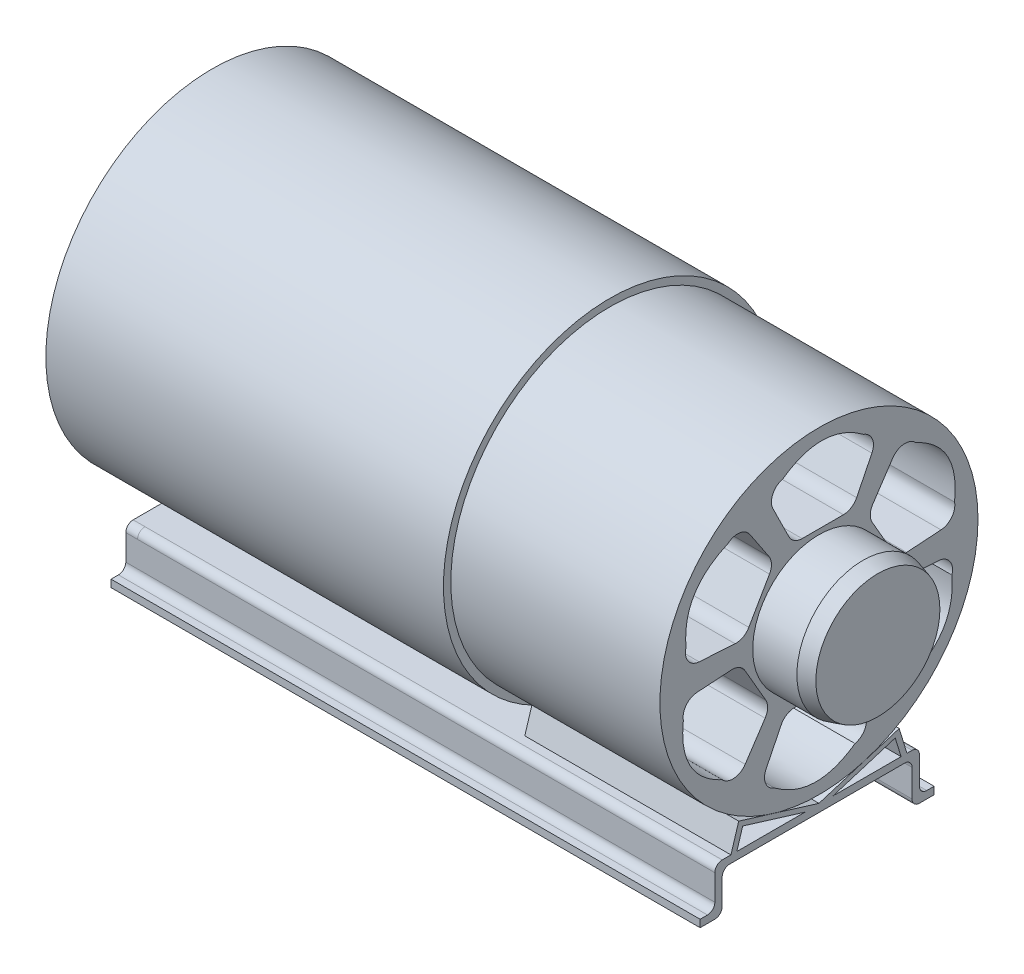
SolidWorks part; units mm, degrees
material "1060 Alloy"
ref_plane "Front Plane" through (0, 0, 0) normal (0, 0, 1) x (1, 0, 0)
ref_plane "Top Plane" through (0, 0, 0) normal (0, 1, 0) x (1, 0, 0)
ref_plane "Right Plane" through (0, 0, 0) normal (1, 0, 0) x (0, 0, -1)
sketch "Sketch1" plane through (0, 0, 0) normal (1, 0, 0) x (0, 0, -1)
  circle A0 centre (0, 0) radius 113
  dimension "D1" = 226
extrude "Boss-Extrude1" add sketch "Sketch1" against normal blind 412
sketch "Sketch2" plane through (0, 0, 0) normal (1, 0, 0) x (0, 0, -1)
  circle A0 centre (0, 0) radius 108
  circle A1 centre (0, 0) radius 113
  dimension "D1" = 216
extrude "Cut-Extrude1" cut sketch "Sketch2" against normal blind 142
sketch "Sketch3" plane through (0, 0, 0) normal (1, 0, 0) x (0, 0, -1)
  circle A0 centre (0, 0) radius 45
  dimension "D1" = 90
extrude "Boss-Extrude2" add sketch "Sketch3" along normal blind 40
chamfer "Chamfer1" distance 10 angle 16 1 edges at (40, 0, -45) first distance on face at (40, 0, -45)
sketch "Sketch4" plane through (0, 0, 0) normal (1, 0, 0) x (0, 0, -1)
  line L0 (-31.2402, 75.8787) -> (-20.392, 53.9645)
  line L1 (-11.43, 48.401) -> (16.6248, 48.401)
  line L2 (25.5919, 53.9748) -> (35.9576, 74.9748)
  line L3 (50.0927, 64.9942) -> (36.5386, 44.6422)
  line L4 (36.2015, 34.0991) -> (50.2288, 9.803)
  line L5 (59.5394, 4.8242) -> (82.9089, 6.3472)
  line L6 (81.333, -10.8845) -> (56.9306, -9.3223)
  line L7 (47.6314, -14.3018) -> (33.6041, -38.5979)
  line L8 (33.9476, -49.1506) -> (46.9513, -68.6276)
  line L9 (31.2402, -75.8787) -> (20.392, -53.9645)
  line L10 (11.43, -48.401) -> (-16.6248, -48.401)
  line L11 (-25.5919, -53.9748) -> (-35.9576, -74.9748)
  line L12 (-50.0927, -64.9942) -> (-36.5386, -44.6422)
  line L13 (-36.2015, -34.0991) -> (-50.2288, -9.803)
  line L14 (-59.5394, -4.8242) -> (-82.9089, -6.3472)
  line L15 (-81.333, 10.8845) -> (-56.9306, 9.3223)
  line L16 (-47.6314, 14.3018) -> (-33.6041, 38.5979)
  line L17 (-33.9476, 49.1506) -> (-46.9513, 68.6276)
  arc A0 (35.9576, 74.9748) -> (30.3376, 88.8243) centre (26.9905, 79.401) ccw
  arc A1 (-31.2402, 75.8787) -> (-24.4733, 90.0713) centre (-22.2782, 80.3152) cw
  arc A2 (-20.392, 53.9645) -> (-11.43, 48.401) centre (-11.43, 58.401) ccw
  arc A3 (16.6248, 48.401) -> (25.5919, 53.9748) centre (16.6248, 58.401) ccw
  arc A4 (50.0927, 64.9942) -> (65.7673, 66.2301) centre (58.4159, 59.4511) cw
  arc A5 (36.5386, 44.6422) -> (36.2015, 34.0991) centre (44.8617, 39.0991) ccw
  arc A6 (50.2288, 9.803) -> (59.5394, 4.8242) centre (58.8891, 14.803) ccw
  arc A7 (82.9089, 6.3472) -> (92.0928, 18.139) centre (82.2586, 16.3261) ccw
  arc A8 (81.333, -10.8845) -> (90.2407, -23.8411) centre (80.6941, -20.8641) cw
  arc A9 (56.9306, -9.3223) -> (47.6314, -14.3018) centre (56.2917, -19.3018) ccw
  arc A10 (33.6041, -38.5979) -> (33.9476, -49.1506) centre (42.2643, -43.5979) ccw
  arc A11 (46.9513, -68.6276) -> (61.7553, -70.6852) centre (55.2681, -63.075) ccw
  arc A12 (31.2402, -75.8787) -> (24.4733, -90.0713) centre (22.2782, -80.3152) cw
  arc A13 (20.392, -53.9645) -> (11.43, -48.401) centre (11.43, -58.401) ccw
  arc A14 (-16.6248, -48.401) -> (-25.5919, -53.9748) centre (-16.6248, -58.401) ccw
  arc A15 (-35.9576, -74.9748) -> (-30.3376, -88.8243) centre (-26.9905, -79.401) ccw
  arc A16 (-50.0927, -64.9942) -> (-65.7673, -66.2301) centre (-58.4159, -59.4511) cw
  arc A17 (-36.5386, -44.6422) -> (-36.2015, -34.0991) centre (-44.8617, -39.0991) ccw
  arc A18 (-50.2288, -9.803) -> (-59.5394, -4.8242) centre (-58.8891, -14.803) ccw
  arc A19 (-82.9089, -6.3472) -> (-92.0928, -18.139) centre (-82.2586, -16.3261) ccw
  arc A20 (-81.333, 10.8845) -> (-90.2407, 23.8411) centre (-80.6941, 20.8641) cw
  arc A21 (-56.9306, 9.3223) -> (-47.6314, 14.3018) centre (-56.2917, 19.3018) ccw
  arc A22 (-33.6041, 38.5979) -> (-33.9476, 49.1506) centre (-42.2643, 43.5979) ccw
  arc A23 (-46.9513, 68.6276) -> (-61.7553, 70.6852) centre (-55.2681, 63.075) ccw
  spline S0 degree 3 poles (30.3376, 88.8243) (20.5234, 96.0661) (2.1757, 102.6494) (-16.0064, 96.0445) (-24.4733, 90.0713) knots 0.076117 0.076117 0.076117 0.076117 0.512929 0.896674 0.896674 0.896674 0.896674
  spline S1 degree 3 poles (92.0928, 18.139) (93.4574, 30.2592) (89.9848, 49.4405) (75.1738, 61.8842) (65.7673, 66.2301) knots 0.076117 0.076117 0.076117 0.076117 0.512929 0.896674 0.896674 0.896674 0.896674
  spline S2 degree 3 poles (61.7553, -70.6852) (72.9339, -65.8069) (87.8091, -53.2089) (91.1802, -34.1603) (90.2407, -23.8411) knots 0.076117 0.076117 0.076117 0.076117 0.512929 0.896674 0.896674 0.896674 0.896674
  spline S3 degree 3 poles (-30.3376, -88.8243) (-20.5234, -96.0661) (-2.1757, -102.6494) (16.0064, -96.0445) (24.4733, -90.0713) knots 0.076117 0.076117 0.076117 0.076117 0.512929 0.896674 0.896674 0.896674 0.896674
  spline S4 degree 3 poles (-92.0928, -18.139) (-93.4574, -30.2592) (-89.9848, -49.4405) (-75.1738, -61.8842) (-65.7673, -66.2301) knots 0.076117 0.076117 0.076117 0.076117 0.512929 0.896674 0.896674 0.896674 0.896674
  spline S5 degree 3 poles (-61.7553, 70.6852) (-72.9339, 65.8069) (-87.8091, 53.2089) (-91.1802, 34.1603) (-90.2407, 23.8411) knots 0.076117 0.076117 0.076117 0.076117 0.512929 0.896674 0.896674 0.896674 0.896674
  point P80 (0, 0)
  dimension "D1" = 10
  dimension "D2" = 6
extrude "Cut-Extrude2" cut sketch "Sketch4" against normal blind 140
sketch "Sketch5" plane through (0, 0, 0) normal (1, 0, 0) x (0, 0, -1)
  line L0 (0, -113) -> (54.4779, -96.2321)
  line L1 (54.4779, -96.2321) -> (59.773, -113.4357)
  line L2 (59.773, -113.4357) -> (55.773, -113.4357)
  line L3 (55.773, -113.4357) -> (51.7735, -100.4415)
  line L4 (51.7735, -100.4415) -> (0, -116.377)
  line L5 (0, -61.5014) -> (0, -90.8439)
  line L6 (-51.7735, -100.4415) -> (0, -116.377)
  line L7 (-55.773, -113.4357) -> (-51.7735, -100.4415)
  line L8 (-59.773, -113.4357) -> (-55.773, -113.4357)
  line L9 (-54.4779, -96.2321) -> (-59.773, -113.4357)
  line L10 (0, -113) -> (-54.4779, -96.2321)
  circle A0 centre (0, 0) radius 113 construction
  dimension "D1" = 4
  dimension "D2" = 18
  dimension "D3" = 57
  dimension "D4" = 54.1704
extrude "Boss-Extrude3" add sketch "Sketch5" against normal blind 140 separate body contours L0 L10 L9 L8 L7 L6 L4 L3 L2 L1 region at (0, -105.7747, -27.5956)
sketch "Sketch7" plane through (0, -113.4357, 0) normal (0, -1, 0) x (1, 0, 0)
  line L0 (0, -108) -> (0, 108) construction
  line L1 (0, 70.7066) -> (-142, 70.7066)
  line L2 (0, 70.7066) -> (0, -68.2082)
  line L3 (0, -68.2082) -> (-142, -68.2082)
  line L4 (-142, 70.7066) -> (-142, -68.2082)
  line L5 (-142, -113) -> (-142, 113) construction
extrude "Boss-Extrude4" add sketch "Sketch7" along normal blind 5
sketch "Sketch8" plane through (0, -118.4357, 0) normal (0, -1, 0) x (1, 0, 0)
  line L0 (0, 70.7066) -> (-142, 70.7066) construction
  line L1 (-142, 70.7066) -> (-392, 70.7066)
  line L2 (-142, 70.7066) -> (-142, -67.7085)
  line L3 (-142, -67.7085) -> (-392, -67.7085)
  line L4 (-392, 70.7066) -> (-392, -67.7085)
  line L5 (-142, -113) -> (-142, 113) construction
  dimension "D1" = 250
extrude "Boss-Extrude5" add sketch "Sketch8" against normal blind 5
sketch "Sketch11" plane through (0, 0, 0) normal (1, 0, 0) x (0, 0, -1)
  line L0 (-65.7066, -113.4357) -> (63.2082, -113.4357)
  line L1 (68.2082, -118.4357) -> (68.2082, -137.0735)
  line L2 (73.2082, -142.0735) -> (78.2082, -142.0735)
  line L3 (78.2082, -142.0735) -> (78.2082, -147.0735)
  line L4 (78.2082, -147.0735) -> (68.2082, -147.0735)
  line L5 (63.2082, -142.0735) -> (63.2082, -123.4357)
  line L6 (68.2082, -118.4357) -> (-70.7066, -118.4357) construction
  line L7 (58.2082, -118.4357) -> (-60.7066, -118.4357)
  line L8 (-65.7066, -123.4357) -> (-65.7066, -140.815)
  line L9 (-70.7066, -145.815) -> (-80.7066, -145.815)
  line L10 (-80.7066, -145.815) -> (-80.7066, -140.815)
  line L11 (-80.7066, -140.815) -> (-75.7066, -140.815)
  line L12 (-70.7066, -135.815) -> (-70.7066, -118.4357)
  arc A0 (63.2082, -113.4357) -> (68.2082, -118.4357) centre (63.2082, -118.4357) cw
  arc A1 (63.2082, -123.4357) -> (58.2082, -118.4357) centre (58.2082, -123.4357) ccw
  arc A2 (-60.7066, -118.4357) -> (-65.7066, -123.4357) centre (-60.7066, -123.4357) ccw
  arc A3 (-65.7066, -113.4357) -> (-70.7066, -118.4357) centre (-65.7066, -118.4357) ccw
  arc A4 (-65.7066, -140.815) -> (-70.7066, -145.815) centre (-70.7066, -140.815) cw
  arc A5 (-75.7066, -140.815) -> (-70.7066, -135.815) centre (-75.7066, -135.815) ccw
  arc A6 (68.2082, -137.0735) -> (73.2082, -142.0735) centre (73.2082, -137.0735) ccw
  arc A7 (68.2082, -147.0735) -> (63.2082, -142.0735) centre (68.2082, -142.0735) cw
  point P18 (68.2082, -113.4357)
  point P21 (63.2082, -118.4357)
  point P24 (-65.7066, -118.4357)
  point P27 (-70.7066, -113.4357)
  point P30 (-65.7066, -145.815)
  point P37 (63.2082, -147.0735)
  dimension "D7" = 5
  dimension "D1" = 15
  dimension "D2" = 15
  dimension "D3" = 5
  dimension "D4" = 5
  dimension "D5" = 5
  dimension "D6" = 5
extrude "Boss-Extrude6" add sketch "Sketch11" against normal blind 400
fillet "Fillet1" radius 5 1 edges at (-71, -113.4357, -68.2082)
fillet "Fillet2" radius 5 1 edges at (-196, -113.4357, 70.7066)
